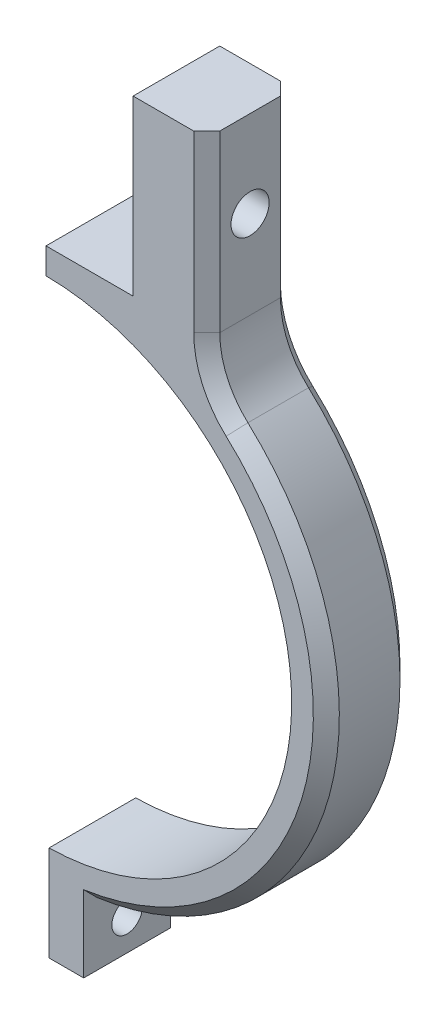
SolidWorks part; units mm, degrees
ref_plane "Ebene vorne" through (0, 0, 0) normal (0, 0, 1) x (1, 0, 0)
ref_plane "Ebene oben" through (0, 0, 0) normal (0, 1, 0) x (1, 0, 0)
ref_plane "Ebene rechts" through (0, 0, 0) normal (1, 0, 0) x (0, 0, -1)
sketch "Skizze1" plane through (0, 0, 0) normal (0, 0, 1) x (1, 0, 0)
  line L0 (0, 0) -> (0, 53.7291) construction
  line L14 (0, 0) -> (0, -44.1347) construction
  line L15 (0.5, -28.4956) -> (0.5, -32.4962)
  line L16 (-0.5, -28.4956) -> (-0.5, -32.4962)
  line L17 (0.5, -32.4962) -> (0.5, -39.4962)
  line L18 (0.5, -39.4962) -> (4.5, -39.4962)
  line L19 (4.5, -39.4962) -> (4.5, -32.187)
  line L20 (-4.5, -39.4962) -> (-4.5, -32.187)
  line L21 (-0.5, -39.4962) -> (-4.5, -39.4962)
  line L22 (-0.5, -32.4962) -> (-0.5, -39.4962)
  line L23 (-10.2, 31.5) -> (-10.2, 51.5)
  line L24 (-10.2, 51.5) -> (-18.7, 51.5)
  line L25 (-18.7, 51.5) -> (-18.7, 26.5812)
  line L26 (-10.2, 31.5) -> (10.2, 31.5)
  line L27 (0, 28.5) -> (12.0002, 28.5) construction
  line L28 (18.7, 51.5) -> (18.7, 26.5812)
  line L29 (10.2, 51.5) -> (18.7, 51.5)
  line L30 (10.2, 31.5) -> (10.2, 51.5)
  arc A0 (0.5, -28.4956) -> (-0.5, -28.4956) centre (0, 0) ccw
  arc A1 (-18.7, 26.5812) -> (-4.5, -32.187) centre (0, 0) ccw
  arc A2 (4.5, -32.187) -> (18.7, 26.5812) centre (0, 0) ccw
  point P10 (0, 33.5025)
  point P11 (0, 31.6594)
  point P17 (0, 31.5)
  point P18 (0, 39.6025)
  dimension "D1" = 57
  dimension "D2" = 4
  dimension "D3" = 20.4
  dimension "D4" = 20
  dimension "D5" = 3
  dimension "D6" = 8.5
  dimension "D10" = 1
  dimension "D11" = 4
  dimension "D12" = 7
extrude "Aufsatz-Linear austragen1" add sketch "Skizze1" along normal blind 10
sketch "Skizze2" plane through (-4.5, 0, 0) normal (-1, 0, 0) x (0, 0, 1)
  line L0 (0, -35.8416) -> (10, -35.8416) construction
  line L1 (0, -32.187) -> (0, -39.4962) construction
  line L2 (10, -32.187) -> (10, -39.4962) construction
  circle A0 centre (5, -35.8416) radius 1.75
  dimension "D1" = 3.5
extrude "Schnitt-Linear austragen1" cut sketch "Skizze2" against normal through all
sketch "Skizze3" plane through (0, 0, 10) normal (0, 0, 1) x (1, 0, 0)
  line L0 (-10.8174, 36.4205) -> (0, 26.8755)
  line L1 (0, 26.8755) -> (11.8484, 37.1414)
  line L2 (11.8484, 37.1414) -> (47.3746, 17.8863)
  line L3 (47.3746, 17.8863) -> (51.4546, -59.0738)
  line L4 (51.4546, -59.0738) -> (-81.1349, -43.2704)
  line L5 (-81.1349, -43.2704) -> (-40.9452, 68.8874)
  line L6 (-40.9452, 68.8874) -> (-10.8174, 36.4205)
extrude "Schnitt-Linear austragen2" [suppressed] cut sketch "Skizze3" against normal through all
sketch "Skizze4" plane through (-18.7, 0, 0) normal (-1, 0, 0) x (0, 0, 1)
  line L0 (5, 51.5) -> (5, 31.5) construction
  line L1 (10, 51.5) -> (0, 51.5) construction
  line L3 (10, 31.5) -> (0, 31.5) construction
  circle A0 centre (5, 41.5) radius 2.2
  dimension "D1" = 4.4
extrude "Schnitt-Linear austragen3" cut sketch "Skizze4" against normal through all
fillet "Verrundung1" radius 10 2 edges at (18.7, 26.5812, 5) (-18.7, 26.5812, 5)
sketch "Skizze5" plane through (-4.5, 0, 0) normal (-1, 0, 0) x (0, 0, 1)
  line L1 (2.25, -38.5916) -> (7.75, -38.5916)
  line L2 (2.25, -38.5916) -> (2.25, -33.0916)
  line L3 (2.25, -33.0916) -> (7.75, -33.0916)
  line L4 (7.75, -38.5916) -> (7.75, -33.0916)
  line L5 (2.25, -38.5916) -> (7.75, -33.0916) construction
  line L6 (2.25, -33.0916) -> (7.75, -38.5916) construction
  point P0 (5, -35.8416)
  dimension "D1" = 5.5
extrude "Schnitt-Linear austragen4" cut sketch "Skizze5" against normal blind 2
chamfer "Fase1" distance 1.5 angle 45 12 edges at (-18.7, 41.4229, 0) (-19.5477, 27.3165, 0) (-31.0366, -9.6425, 0) (18.7, 41.4229, 0) (19.5477, 27.3165, 0) (31.0366, -9.6425, 0) (-18.7, 41.4229, 10) (-19.5477, 27.3165, 10) (-31.0366, -9.6425, 10) (18.7, 41.4229, 10) (19.5477, 27.3165, 10) (31.0366, -9.6425, 10)
sketch "Skizze6" plane through (0, 0, 0) normal (0, 0, 1) x (1, 0, 0)
  line L0 (0, -82.9146) -> (0, 27.8305)
  line L1 (0, 82.9146) -> (-62.1698, 71.0203)
  line L2 (-62.1698, 71.0203) -> (-62.1698, -54.9185)
  line L3 (-62.1698, -54.9185) -> (0, -82.9146)
  line L4 (0, 32.2084) -> (0.15, 32.2084)
  line L5 (0.15, 32.2084) -> (0.15, 27.8305)
  line L6 (0.15, 27.8305) -> (0, 27.8305)
  line L7 (0, 32.2084) -> (0, 82.9146)
  point P4 (0, 0)
  dimension "D1" = 0.15
extrude "Schnitt-Linear austragen5" cut sketch "Skizze6" along normal through all
